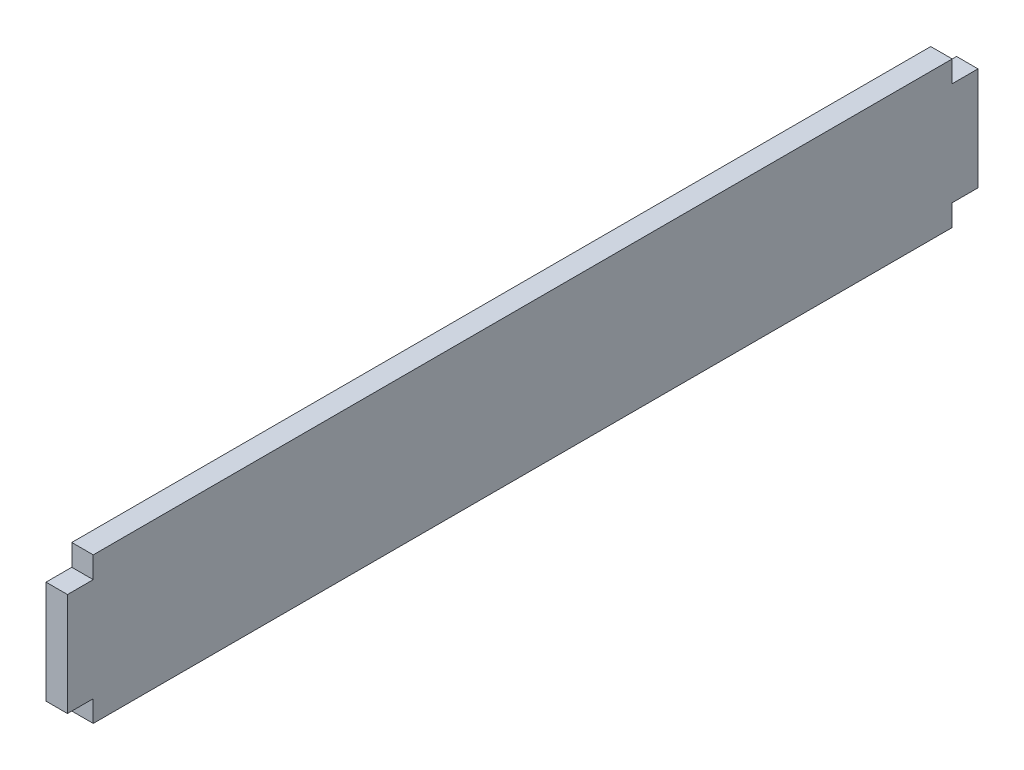
SolidWorks part; units mm, degrees
ref_plane "Front Plane" through (0, 0, 0) normal (0, 0, 1) x (1, 0, 0)
ref_plane "Top Plane" through (0, 0, 0) normal (0, 1, 0) x (1, 0, 0)
ref_plane "Right Plane" through (0, 0, 0) normal (1, 0, 0) x (0, 0, -1)
sketch "Sketch1" plane through (0, 0, 0) normal (0, 0, 1) x (1, 0, 0)
  line L0 (-1.25, -6) -> (-1.25, 6)
  line L1 (-1.25, 8.5) -> (1.25, 8.5)
  line L2 (-1.25, 8.5) -> (-1.25, -8.5)
  line L3 (-1.25, -8.5) -> (1.25, -8.5)
  line L4 (1.25, 8.5) -> (1.25, -8.5)
  line L5 (-1.25, 8.5) -> (1.25, -8.5) construction
  line L6 (-1.25, -8.5) -> (1.25, 8.5) construction
  line L9 (-1.25, 6) -> (1.25, 6)
  line L10 (1.25, -6) -> (-1.25, -6)
  line L11 (1.25, 6) -> (1.25, -6)
  point P0 (0, 0)
  dimension "D1" = 2.5
  dimension "D2" = 17
  dimension "D3" = 12
  dimension "D4" = 6
extrude "Boss-Extrude1" add sketch "Sketch1" along normal blind 100 contours L4 L1 L2 | L2 L3 L4 | L2 L4 region at (0, -7.25, 0) region at (0, 0, 0) region at (0, 7.25, 0)
extrude "Boss-Extrude2" add sketch "Sketch1<3>" against normal blind 3 contours L2 L4 region at (0, 0, 0)
sketch "Sketch1<3>" plane through (0, 0, 0) normal (0, 0, 1) x (1, 0, 0) same geometry as "Sketch1"
ref_plane "Plane1" through (0, 0, 50) normal (0, 0, -1) x (-1, 0, 0)
mirror "Mirror1" about plane through (0, 0, 50) normal (0, 0, -1) of "Boss-Extrude2"
